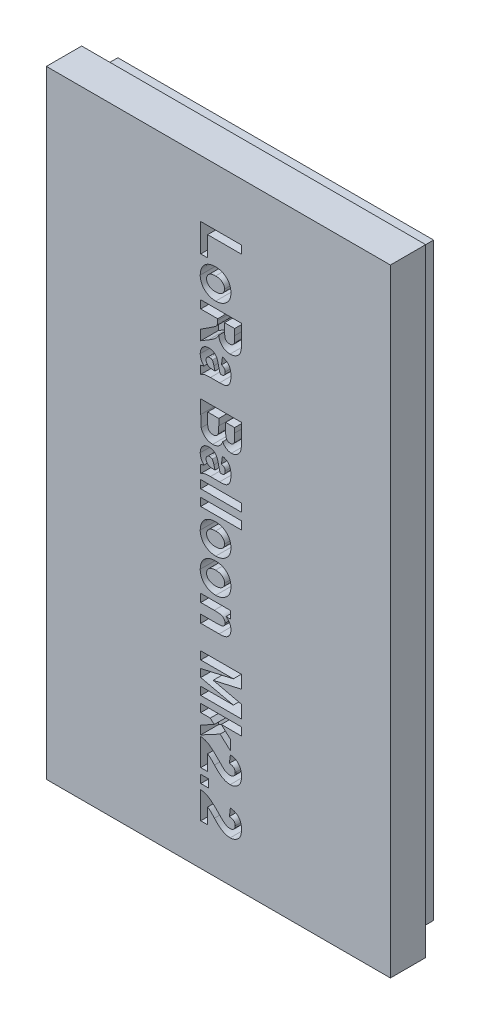
SolidWorks part; units mm, degrees
ref_plane "Front Plane" through (0, 0, 0) normal (0, 0, 1) x (1, 0, 0)
ref_plane "Top Plane" through (0, 0, 0) normal (0, 1, 0) x (1, 0, 0)
ref_plane "Right Plane" through (0, 0, 0) normal (1, 0, 0) x (0, 0, -1)
sketch "Sketch1" plane through (0, 0, 0) normal (0, 0, 1) x (1, 0, 0)
  line L1 (0, 0) -> (39, 0)
  line L2 (0, 0) -> (0, 70)
  line L3 (0, 70) -> (39, 70)
  line L4 (39, 0) -> (39, 70)
  dimension "D1" = 70
  dimension "D2" = 39
extrude "Base" add sketch "Sketch1" along normal blind 4
sketch "Sketch2" plane through (0, 0, 0) normal (0, 0, -1) x (-1, 0, 0)
  line L0 (-39, 0) -> (-39, 70) construction
  line L1 (-37.4, 68.4) -> (-35.6, 68.4)
  line L2 (-37.4, 68.4) -> (-37.4, 1.6)
  line L3 (-37.4, 1.6) -> (-35.6, 1.6)
  line L4 (-35.6, 68.4) -> (-35.6, 1.6)
  line L5 (0, 0) -> (-39, 0) construction
  line L6 (0, 70) -> (0, 0) construction
  line L7 (-35.6, 1.6) -> (-1.6, 1.6)
  line L8 (-35.6, 1.6) -> (-35.6, 3.4)
  line L9 (-35.6, 3.4) -> (-1.6, 3.4)
  line L10 (-1.6, 1.6) -> (-1.6, 3.4)
  line L12 (-39, 70) -> (0, 70) construction
  line L13 (-39, 35) -> (0, 35) construction
  line L14 (-19.5, 70) -> (-19.5, 0) construction
  line L15 (-35.6, 66.6) -> (-1.6, 66.6)
  line L16 (-1.6, 68.4) -> (-1.6, 66.6)
  line L17 (-35.6, 68.4) -> (-1.6, 68.4)
  line L18 (-35.6, 68.4) -> (-35.6, 66.6)
  line L19 (-1.6, 1.6) -> (-3.4, 1.6)
  line L20 (-3.4, 68.4) -> (-3.4, 1.6)
  line L21 (-1.6, 68.4) -> (-3.4, 68.4)
  line L22 (-1.6, 68.4) -> (-1.6, 1.6)
  dimension "D1" = 1.6
  dimension "D2" = 1.8
  dimension "D3" = 1.6
  dimension "D4" = 1.8
extrude "Mount" add sketch "Sketch2" along normal blind 2.5 contours L4 L1 L2 L3 | L22 L15 L20 L9 | L20 L9 L4 L7 | L9 L20 L7 L10 | L17 L20 L15 L16 | L20 L17 L4 L15 region at (36.5, 35, 0) region at (19.5, 67.5, 0) region at (2.5, 67.5, 0) region at (19.5, 2.5, 0) region at (2.5, 35, 0) region at (2.5, 2.5, 0)
sketch "Sketch3" plane through (0, 0, 4) normal (0, 0, 1) x (1, 0, 0)
  line L0 (17.5, 0) -> (17.5, 64) construction
  line L4 (0, 0) -> (39, 0) construction
  line L6 (0, 70) -> (0, 0) construction
  text T0 "<b>LoRa Balloon Mk2.2</b>" font "Arial Narrow" height in points 18
  dimension "D1" = 17.5
  dimension "D2" = 64
extrude "Logo" cut sketch "Sketch3" against normal blind 2
